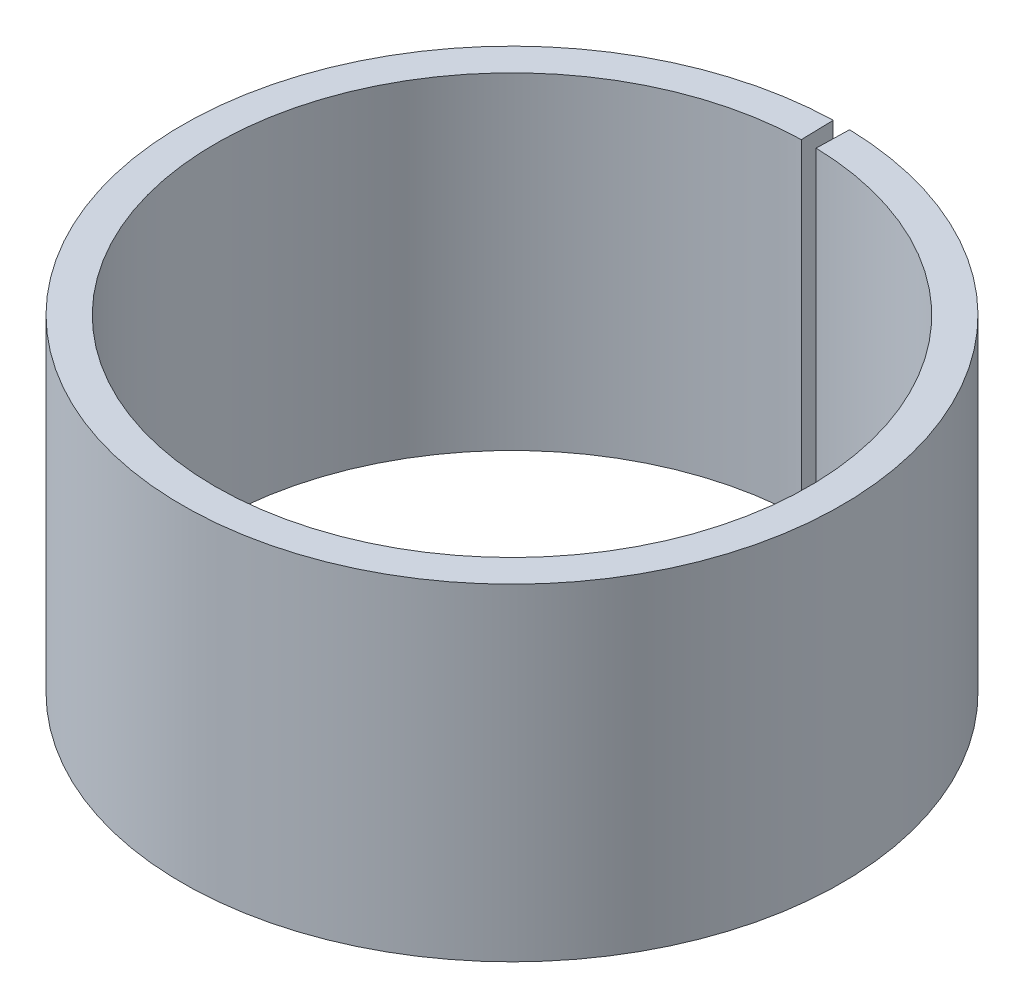
SolidWorks part; units mm, degrees
material "ABS"
ref_plane "Front Plane" through (0, 0, 0) normal (0, 0, 1) x (1, 0, 0)
ref_plane "Top Plane" through (0, 0, 0) normal (0, 1, 0) x (1, 0, 0)
ref_plane "Right Plane" through (0, 0, 0) normal (1, 0, 0) x (0, 0, -1)
sketch "Sketch1" plane through (0, 0, 0) normal (0, 1, 0) x (1, 0, 0)
  line L0 (0, 0) -> (0, 51.1652) construction
  line L1 (1.1439, 46.0868) -> (1.27, 51.1652)
  line L2 (-1.1439, 46.0868) -> (-1.27, 51.1652)
  line L3 (-1.1439, 46.0868) -> (0, 0) construction
  line L4 (0, 0) -> (1.1439, 46.0868) construction
  arc A0 (-1.27, 51.1652) -> (1.27, 51.1652) centre (0, 0) ccw
  arc A1 (-1.1439, 46.0868) -> (1.1439, 46.0868) centre (0, 0) ccw
  point P1 (0, 55.1113)
  point P3 (-0.0286, 1.1529)
  point P4 (0, 0)
  dimension "D1" = 102.362
  dimension "D2" = 5.08
  dimension "D3" = 2.54
extrude "Boss-Extrude1" add sketch "Sketch1" along normal blind 50.8
